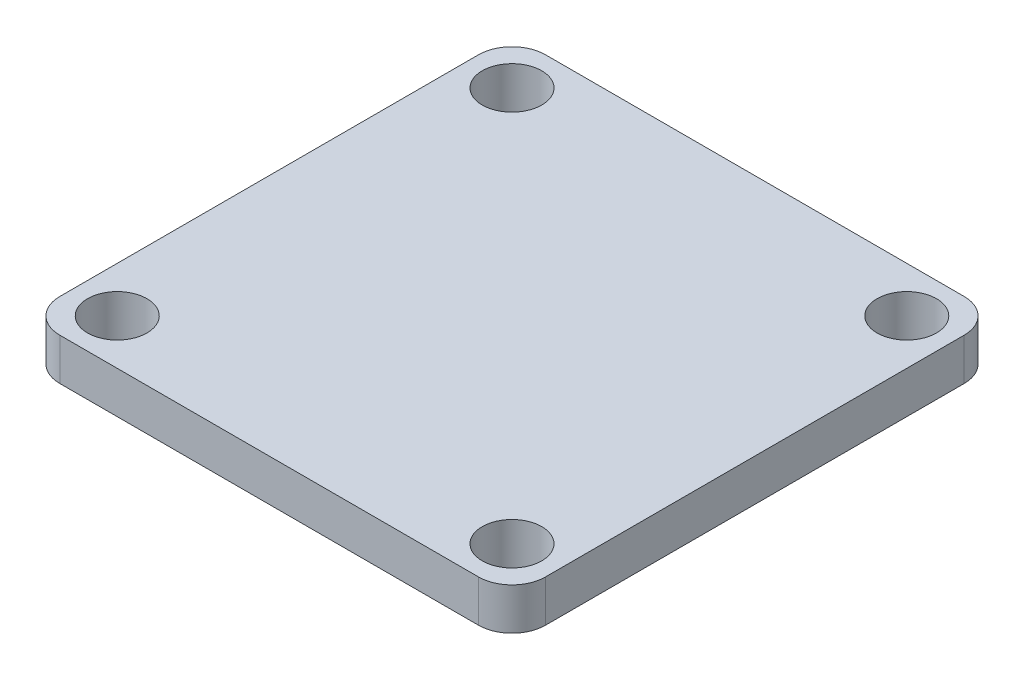
SolidWorks part; units mm, degrees
ref_plane "Front Plane" through (0, 0, 0) normal (0, 0, 1) x (1, 0, 0)
ref_plane "Top Plane" through (0, 0, 0) normal (0, 1, 0) x (1, 0, 0)
ref_plane "Right Plane" through (0, 0, 0) normal (1, 0, 0) x (0, 0, -1)
sketch "Sketch1" plane through (0, 0, 0) normal (0, 1, 0) x (1, 0, 0)
  line L0 (-23.57, 0) -> (23.57, 0) construction
  line L1 (-29, -29) -> (29, -29)
  line L2 (-29, -29) -> (-29, 29)
  line L3 (-29, 29) -> (29, 29)
  line L4 (29, -29) -> (29, 29)
  line L5 (-29, -29) -> (29, 29) construction
  line L6 (-29, 29) -> (29, -29) construction
  line L7 (-23.57, -29) -> (-23.57, -23.57) construction
  line L8 (-23.57, -23.57) -> (-29, -23.57) construction
  line L9 (0, -29) -> (0, 29) construction
  circle A0 centre (-23.57, -23.57) radius 2.55 construction
  circle A1 centre (23.57, -23.57) radius 2.55 construction
  circle A2 centre (23.57, 23.57) radius 2.55 construction
  circle A3 centre (-23.57, 23.57) radius 2.55 construction
  circle A4 centre (-23.57, 23.57) radius 3.55
  circle A5 centre (23.57, 23.57) radius 3.55
  circle A6 centre (23.57, -23.57) radius 3.55
  circle A7 centre (-23.57, -23.57) radius 3.55
  point P0 (0, 0)
  point P9 (0, 0)
  dimension "D3" = 5.1
  dimension "D4" = 7.1
  dimension "D1" = 58
  dimension "D2" = 47.14
extrude "Boss-Extrude1" add sketch "Sketch1" along normal blind 5
fillet "Fillet1" radius 4 4 edges at (-29, 2.5, 29) (29, 2.5, 29) (29, 2.5, -29) (-29, 2.5, -29)
